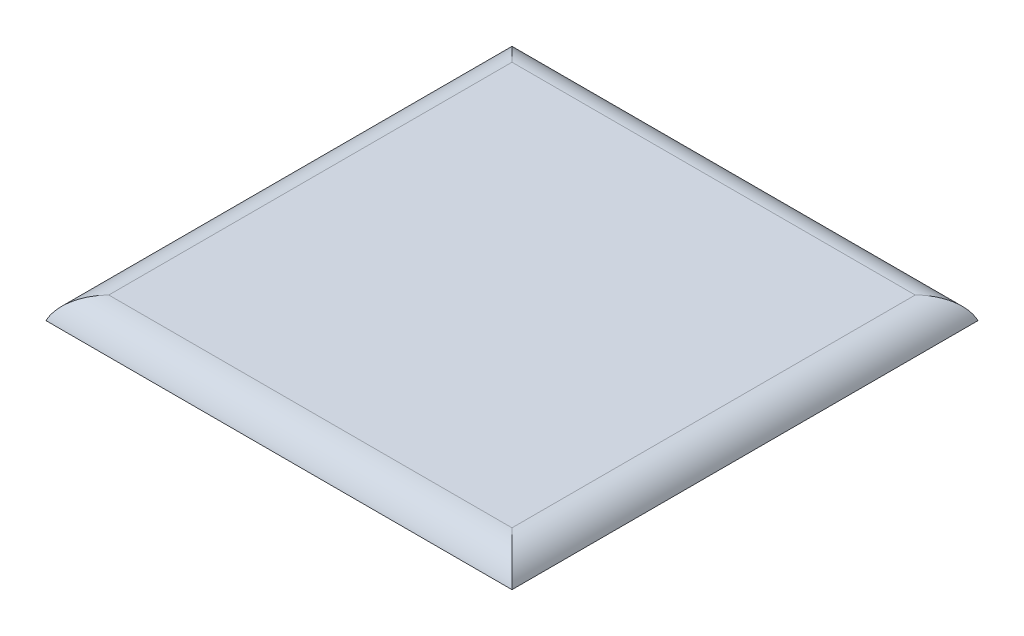
SolidWorks part; units mm, degrees
ref_plane "Front Plane" through (0, 0, 0) normal (0, 0, 1) x (1, 0, 0)
ref_plane "Top Plane" through (0, 0, 0) normal (0, 1, 0) x (1, 0, 0)
ref_plane "Right Plane" through (0, 0, 0) normal (1, 0, 0) x (0, 0, -1)
sketch "Sketch1" plane through (0, 0, 0) normal (0, 1, 0) x (1, 0, 0)
  line L0 (-88.4681, 130.1106) -> (-75.7787, 119.566)
  line L1 (-88.4681, 130.1106) -> (121.5319, 130.1106)
  line L2 (-88.4681, 130.1106) -> (-88.4681, -79.8894)
  line L3 (-88.4681, -79.8894) -> (121.5319, -79.8894)
  line L4 (121.5319, 130.1106) -> (121.5319, -79.8894)
  line L5 (-75.7787, 119.566) -> (108.8426, 119.566)
  line L6 (-75.7787, 119.566) -> (-75.7787, -69.3447)
  line L7 (-75.7787, -69.3447) -> (108.8426, -69.3447)
  line L8 (108.8426, 119.566) -> (108.8426, -69.3447)
  line L9 (108.8426, 119.566) -> (121.5319, 130.1106)
  line L10 (108.8426, -69.3447) -> (121.5319, -79.8894)
  dimension "D1" = 210
  dimension "D2" = 210
extrude "Boss-Extrude1" add sketch "Sketch1" along normal blind 10 contours L5 L9 L1 L0 | L8 L10 L4 L9 | L10 L7 L6 L0 L2 L3 | L8 L5 L6 L7 region at (16.5319, 0, -124.9513) region at (-84.0215, 0, -122.5542) region at (16.5319, 0, -25.1106) region at (115.299, 0, -25.1106)
fillet "Fillet2" radius 15 4 edges at (121.5319, 10, -25.1106) (16.5319, 10, -130.1106) (-88.4681, 10, -25.1106) (16.5319, 10, 79.8894)
